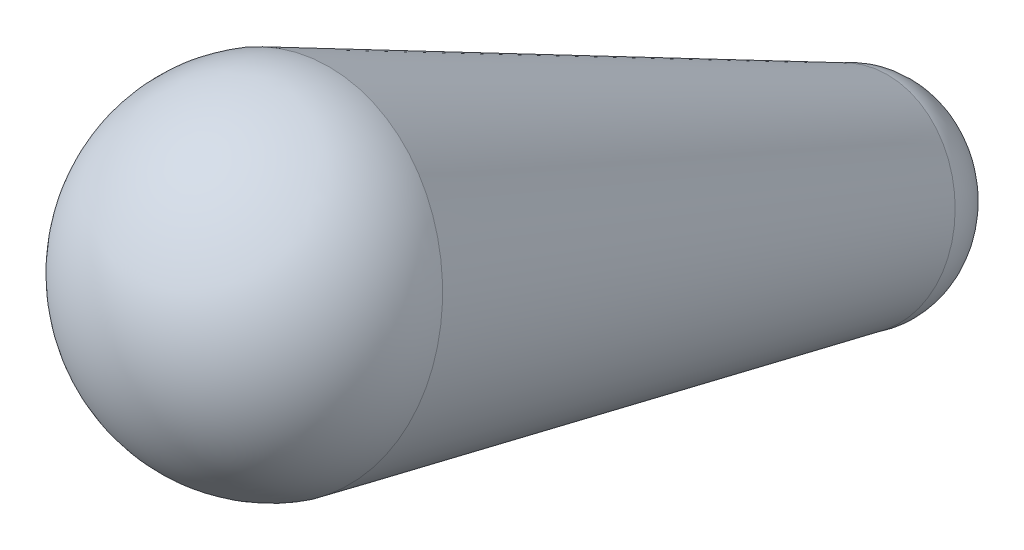
SolidWorks part; units mm, degrees
ref_plane "Front Plane" through (0, 0, 0) normal (0, 0, 1) x (1, 0, 0)
ref_plane "Top Plane" through (0, 0, 0) normal (0, 1, 0) x (1, 0, 0)
ref_plane "Right Plane" through (0, 0, 0) normal (1, 0, 0) x (0, 0, -1)
sketch "Top Contour" plane through (0, 0, 0) normal (1, 0, 0) x (0, 0, -1)
  line L0 (189.3211, -51.6959) -> (211.8805, -60.4148) construction
  line L1 (189.3211, -51.6959) -> (149.4591, -69.9444) construction
  line L2 (149.4591, -69.9444) -> (126.4413, -51.6959) construction
ref_plane "Plane1" through (0, -51.6959, -189.3211) normal (0, -0.3605, -0.9328) x (-1, 0, 0)
sketch "Sketch1" plane through (0, -51.6959, -189.3211) normal (0, -0.3605, -0.9328) x (-1, 0, 0)
  circle A0 centre (0, 0) radius 6.2689
extrude "Boss-Extrude1" add sketch "Sketch1" along normal up to vertex (24.1857 mm away) draft 6 up to point (0, -60.4148, -211.8805)
dome "Dome1" faces to dome 1 distance 6 reverse direction no elliptical dome yes face at (0, -45.8486, -191.581) parameters "D1"=6
dome "Dome2" faces to dome 1 distance 3 reverse direction no elliptical dome yes face at (0, -56.9386, -213.224) parameters "D1"=3
ref_axis "Axis1" through (0, -51.6959, -189.3211) along (1, 0, 0)
ref_axis "Axis2" through (0, -60.4148, -211.8805) along (1, 0, 0)
